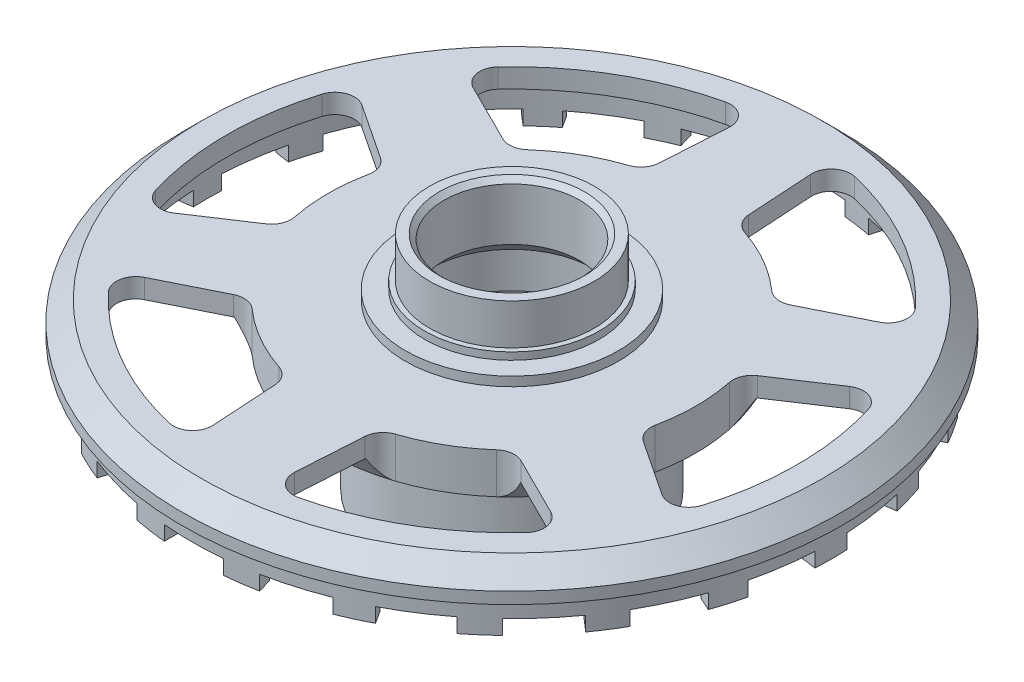
SolidWorks part; units mm, degrees
ref_plane "Front Plane" through (0, 0, 0) normal (0, 0, 1) x (1, 0, 0)
ref_plane "Top Plane" through (0, 0, 0) normal (0, 1, 0) x (1, 0, 0)
ref_plane "Right Plane" through (0, 0, 0) normal (1, 0, 0) x (0, 0, -1)
ref_axis "Axis1" through (0, 0, 0) along (0, 1, 0)
sketch "Sketch1" plane through (0, 0, 0) normal (0, 0, 1) x (1, 0, 0)
  line L0 (-32.95, 8) -> (-32.95, 4.5)
  line L2 (-32.95, 4.5) -> (-31.45, 4.5)
  line L3 (-31.45, 4.5) -> (-31.45, 8.2)
  line L4 (-32.95, 8) -> (-34, 8)
  line L5 (-34, 8) -> (-34, 8.5)
  line L7 (-11, 12.15) -> (-9, 12.15)
  line L8 (-9, 12.15) -> (-9, 12.9)
  line L9 (-9, 12.9) -> (-8.5, 12.9)
  line L10 (-8.5, 12.9) -> (-8.5, 17.1)
  line L11 (-8.5, 17.1) -> (-7, 17.1)
  line L12 (-7, 17.1) -> (-7, 11.2)
  line L15 (0, 0) -> (0, -50000) construction
  line L16 (-30.45, 9.2) -> (-31.45, 8.2)
  line L18 (-8.5, 9.7) -> (-8.5, 6)
  line L25 (-12.99, 4) -> (-12.49, 4)
  line L29 (-20.2602, 9.2) -> (-30.45, 9.2)
  line L32 (-34, 9.2) -> (-34, 8.5)
  line L34 (-32, 11.2) -> (-11, 11.2)
  line L35 (-34, 9.2) -> (-32, 11.2)
  line L36 (-11, 12.15) -> (-11, 11.2)
  line L38 (20.75, 6) -> (-20.75, 6) construction
  line L39 (-20.2602, 9.2) -> (-18.99, 7)
  line L40 (-18.99, 7) -> (-12.99, 7)
  line L41 (-12.99, 7) -> (-12.99, 4)
  line L44 (-12.49, 4) -> (-12.49, -6)
  line L45 (-12.49, -6) -> (-9, -6)
  line L46 (-9, -6) -> (-9, 6)
  line L47 (-9, 6) -> (-8.5, 6)
  line L48 (8.2033, 6) -> (-8.2033, 6) construction
  line L49 (-8.2033, -6) -> (8.2033, -6) construction
  line L50 (12.75, 4) -> (-12.75, 4) construction
  line L51 (-7, 11.2) -> (-8.5, 9.7)
  point P6 (-31.45, 9.2)
  point P19 (-34, 11.2)
  dimension "D1" = 3.5
  dimension "D2" = 1.5
  dimension "D3" = 17
  dimension "D4" = 4.2
  dimension "D5" = 0.75
  dimension "D6" = 0.5
  dimension "D7" = 1.5
  dimension "D8" = 135
  dimension "D10" = 65.9
  dimension "D11" = 22
  dimension "D12" = 0.5
  dimension "D13" = 18
  dimension "D15" = 0.5
  dimension "D16" = 0.95
  dimension "D17" = 6
  dimension "D18" = 0.5
  dimension "D19" = 2
  dimension "D20" = 3.2
  dimension "D21" = 1
  dimension "D22" = 120
  dimension "D23" = 24.98
revolve "Revolve1" add sketch "Sketch1" angle 360 about L15
sketch "Sketch2" plane through (0, 0, 0) normal (0, 0, 1) x (1, 0, 0)
  line L1 (-3.05, -0.7629) -> (3.05, -0.7629)
  line L2 (-3.05, -0.7629) -> (-3.05, 6)
  line L3 (-3.05, 6) -> (3.05, 6)
  line L4 (3.05, -0.7629) -> (3.05, 6)
  line L5 (-32.95, 8) -> (32.95, 8) construction
  point P4 (0, -0.7629)
  dimension "D1" = 6.1
  dimension "D2" = 2
extrude "Cut-Extrude2" cut sketch "Sketch2" along normal through all from offset 20
pattern_circular "CirPattern1" count 22 over 360 about axis through (0, 0, 0) along (0, 1, 0) of "Cut-Extrude2"
sketch "Sketch4" plane through (0, 0, 0) normal (0, 1, 0) x (1, 0, 0)
  circle A0 centre (-16, 0) radius 2.06
  dimension "D1" = 4.12
  dimension "D2" = 16
extrude "Cut-Extrude3" cut sketch "Sketch4" along normal blind 3 from surface starting at face at (-12.99, 7, 0)
pattern_circular "CirPattern2" count 24 over 360 about axis through (0, 0, 0) along (0, 1, 0) of "Cut-Extrude3"
sketch "Sketch5" plane through (0, 0, 0) normal (0, 1, 0) x (1, 0, 0)
  circle A0 centre (0, 0) radius 16
extrude "Cut-Extrude-Thin1" cut sketch "Sketch5" along normal up to surface (10 mm away) thin up to face at (-13.94, 10, 0) thin type mid plane wall 2
chamfer "Chamfer1" distance 0.5 angle 45 1 edges at (-7, 17.1, 0)
sketch "Sketch6" plane through (0, 0, 0) normal (0, 1, 0) x (1, 0, 0)
  line L0 (0, 0) -> (-50000, 0) construction
  line L1 (-27.2859, -11.0807) -> (-18.2867, -5.1202)
  line L2 (-18.2867, 5.1202) -> (-27.2859, 11.0807)
  arc A0 (-27.2859, -11.0807) -> (-27.2859, 11.0807) centre (0, 0) cw
  arc A1 (-18.2867, -5.1202) -> (-18.2867, 5.1202) centre (0, 0) cw
  circle A2 centre (0, 0) radius 30.45 construction
  circle A3 centre (0, 0) radius 18.99 construction
  point P9 (-29.45, 0)
  point P10 (-18.99, 0)
  dimension "D1" = 1
extrude "Cut-Extrude4" cut sketch "Sketch6" along normal through all
fillet "Fillet1" radius 2 4 edges at (-27.2859, 10.2, 11.0807) (-18.2867, 9.1, 5.1202) (-18.2867, 9.1, -5.1202) (-27.2859, 10.2, -11.0807)
pattern_circular "CirPattern3" count 6 over 360 about axis through (0, 0, 0) along (0, 1, 0) of "Cut-Extrude4", "Fillet1"
chamfer "Chamfer2" distance 0.25 angle 45 2 edges at (-9, -6, 0) (-12.49, -6, 0)
